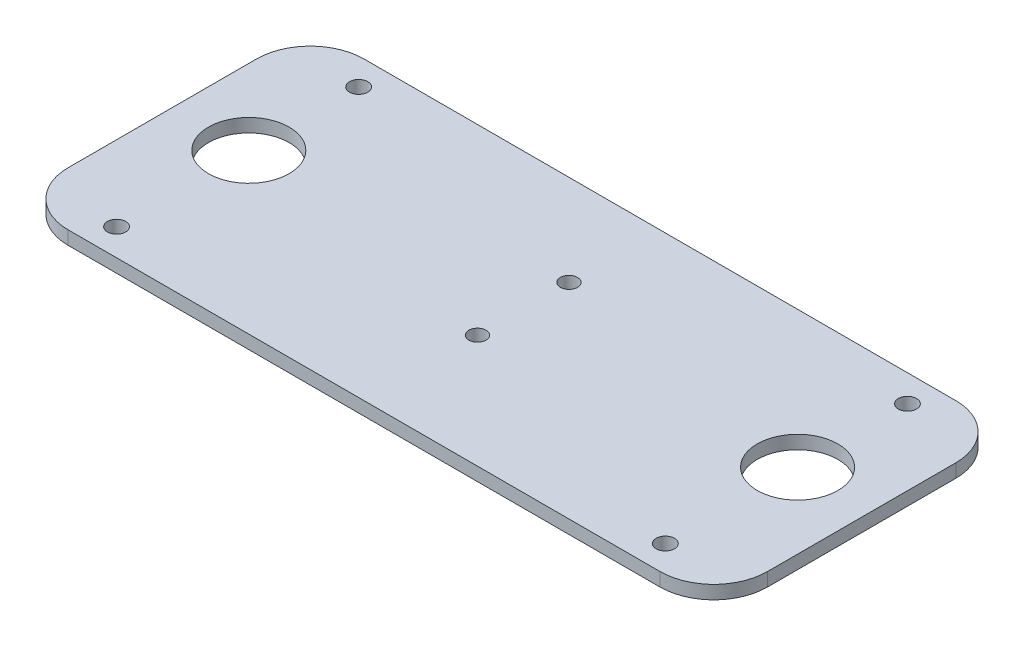
SolidWorks part; units mm, degrees
ref_plane "Front Plane" through (0, 0, 0) normal (0, 0, 1) x (1, 0, 0)
ref_plane "Top Plane" through (0, 0, 0) normal (0, 1, 0) x (1, 0, 0)
ref_plane "Right Plane" through (0, 0, 0) normal (1, 0, 0) x (0, 0, -1)
sketch "Sketch1" plane through (0, 0, 0) normal (0, 1, 0) x (1, 0, 0)
  line L1 (10, 0) -> (120, 0)
  line L2 (0, 10) -> (0, 45)
  line L3 (10, 55) -> (120, 55)
  line L4 (130, 10) -> (130, 45)
  arc A0 (10, 55) -> (0, 45) centre (10, 45) ccw
  arc A1 (0, 10) -> (10, 0) centre (10, 10) ccw
  arc A2 (130, 10) -> (120, 0) centre (120, 10) cw
  arc A3 (120, 55) -> (130, 45) centre (120, 45) cw
  point P7 (0, 55)
  point P10 (0, 0)
  point P13 (130, 0)
  dimension "D3" = 10
  dimension "D4" = 10
  dimension "D5" = 10
  dimension "D6" = 10
  dimension "D1" = 130
  dimension "D2" = 55
extrude "Boss-Extrude1" add sketch "Sketch1" along normal blind 2.5
sketch "Sketch2" plane through (0, 2.5, 0) normal (0, 1, 0) x (1, 0, 0)
  line L0 (0, 45) -> (0, 10) construction
  line L1 (10, 0) -> (120, 0) construction
  line L2 (120, 55) -> (10, 55) construction
  line L3 (65, 53.2946) -> (65, -1.7054) construction
  circle A0 centre (14, 5) radius 1.7
  circle A1 centre (14, 50) radius 1.7
  circle A2 centre (116, 5) radius 1.7
  circle A3 centre (116, 50) radius 1.7
  circle A4 centre (14, 29.5783) radius 7.5
  circle A5 centre (116, 29.5783) radius 7.5
  circle A6 centre (65, 38.0783) radius 1.6
  circle A7 centre (65, 21.0783) radius 1.6
  point P24 (0, 0)
  dimension "D2" = 14
  dimension "D3" = 5
  dimension "D5" = 5
extrude "Cut-Extrude1" cut sketch "Sketch2" against normal through all
